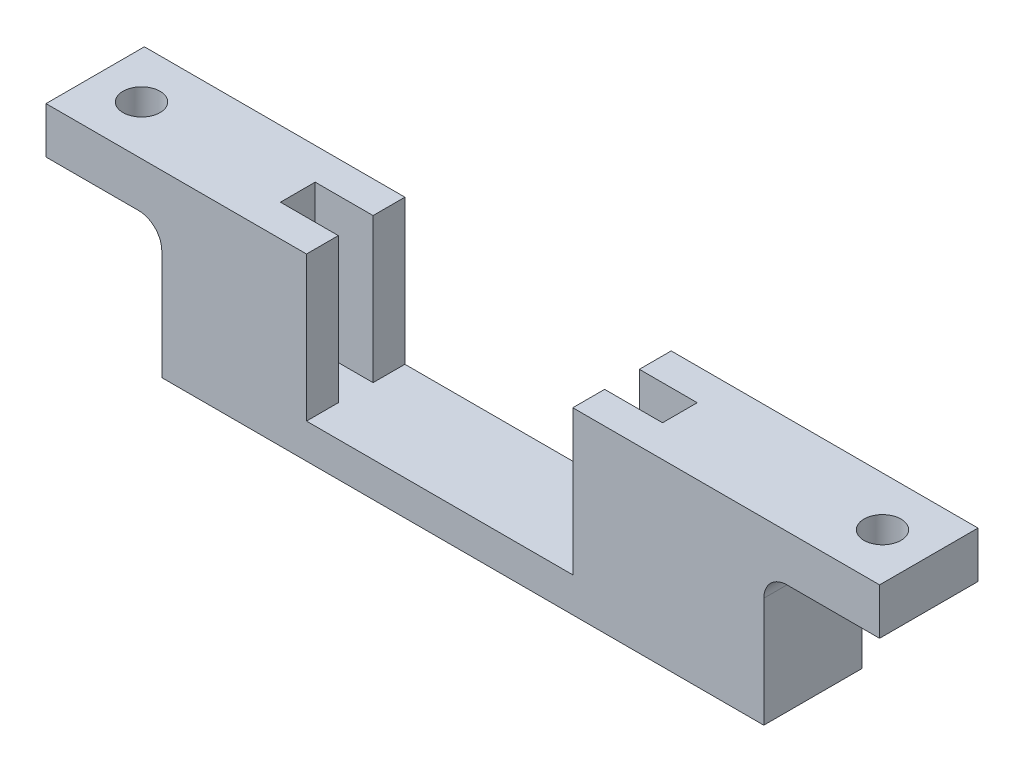
SolidWorks part; units mm, degrees
ref_plane "Front Plane" through (0, 0, 0) normal (0, 0, 1) x (1, 0, 0)
ref_plane "Top Plane" through (0, 0, 0) normal (0, 1, 0) x (1, 0, 0)
ref_plane "Right Plane" through (0, 0, 0) normal (1, 0, 0) x (0, 0, -1)
sketch "Sketch1" plane through (0, 0, 0) normal (0, 1, 0) x (1, 0, 0)
  line L1 (-36, 4.25) -> (36, 4.25)
  line L2 (-36, 4.25) -> (-36, -4.25)
  line L3 (-36, -4.25) -> (36, -4.25)
  line L4 (36, 4.25) -> (36, -4.25)
  line L5 (-36, 4.25) -> (36, -4.25) construction
  line L6 (-36, -4.25) -> (36, 4.25) construction
  point P0 (0, 0)
  dimension "D1" = 8.5
  dimension "D2" = 72
extrude "Boss-Extrude1" add sketch "Sketch1" along normal blind 15.5
sketch "Sketch2" plane through (0, 15.5, 0) normal (0, 1, 0) x (1, 0, 0)
  line L0 (-37.0107, -28.8692) -> (-13.0693, 36.9092) construction
  line L1 (16.1982, -28.8692) -> (40.1396, 36.9092) construction
  line L3 (-13.5, -4.25) -> (9.5, -4.25)
  line L8 (-13.5, -4.25) -> (-13.5, 4.25)
  line L9 (-13.5, 4.25) -> (9.5, 4.25)
  line L10 (9.5, -4.25) -> (9.5, 4.25)
  line L11 (-13.5, -4.25) -> (9.5, 4.25) construction
  line L12 (-13.5, 4.25) -> (9.5, -4.25) construction
  line L13 (-18.5, -1.5) -> (-13.5, -1.5)
  line L14 (-18.5, -1.5) -> (-18.5, 1.5)
  line L15 (-18.5, 1.5) -> (-13.5, 1.5)
  line L16 (-13.5, -1.5) -> (-13.5, 1.5)
  line L17 (-18.5, -1.5) -> (-13.5, 1.5) construction
  line L18 (-18.5, 1.5) -> (-13.5, -1.5) construction
  line L19 (9.5, -1.5) -> (14.5, -1.5)
  line L20 (9.5, -1.5) -> (9.5, 1.5)
  line L21 (9.5, 1.5) -> (14.5, 1.5)
  line L22 (14.5, -1.5) -> (14.5, 1.5)
  line L23 (9.5, -1.5) -> (14.5, 1.5) construction
  line L24 (9.5, 1.5) -> (14.5, -1.5) construction
  line L25 (36, 4.25) -> (-36, 4.25) construction
  line L26 (-36, 4.25) -> (-36, -4.25) construction
  point P2 (-2, 0)
  point P9 (12, 0)
  point P10 (-16, 0)
  point P22 (0, 0)
  point P23 (0, 0)
  point P24 (-25.04, 4.02)
  point P30 (-25.04, 4.02)
  line M15 (36, 4.25) -> (-36, 4.25)
  line M17 (-36, -4.25) -> (36, -4.25)
  dimension "D1" = 20
  dimension "D2" = 3
  dimension "D3" = 23
  dimension "D4" = 5
  dimension "D5" = 3
  dimension "D6" = 5
  dimension "D7" = 2
  dimension "D8" = 50
  dimension "D9" = 53.2089
  dimension "D10" = 6.54
  dimension "D11" = 2.52
  dimension "D12" = 70
extrude "Cut-Extrude1" cut sketch "Sketch2" against normal blind 12.5 contours L10 L8 M17 M15 | L15 L14 L13 L8 | L19 L22 L21 L10 region at (-2, 15.5, 0) region at (-16, 15.5, 0) region at (12, 15.5, 0)
sketch "Sketch3" plane through (0, 0, 0) normal (0, -1, 0) x (1, 0, 0)
  line L0 (36, -4.25) -> (-36, -4.25) construction
  line L1 (-36, 4.25) -> (-26, 4.25)
  line L2 (-36, 4.25) -> (-36, -4.25)
  line L3 (-36, -4.25) -> (-26, -4.25)
  line L4 (-26, 4.25) -> (-26, -4.25)
  line L6 (36, 4.25) -> (26, 4.25)
  line L7 (36, 4.25) -> (36, -4.25)
  line L8 (36, -4.25) -> (26, -4.25)
  line L9 (26, 4.25) -> (26, -4.25)
  dimension "D1" = 10
  dimension "D2" = 10
extrude "Cut-Extrude2" cut sketch "Sketch3" against normal blind 11.5
sketch "Sketch4" plane through (0, 15.5, 0) normal (0, 1, 0) x (1, 0, 0)
  line L0 (-36, 0) -> (36, 0) construction
  line L1 (-36, 4.25) -> (-36, -4.25) construction
  line L2 (36, -4.25) -> (36, 4.25) construction
  circle A0 centre (-32, 0) radius 1.6
  circle A1 centre (32, 0) radius 1.6
  point P10 (32.3146, 0)
  dimension "D1" = 3.2
  dimension "D2" = 3.2
  dimension "D3" = 4
  dimension "D4" = 4
extrude "Cut-Extrude3" cut sketch "Sketch4" against normal through all
fillet "Fillet1" radius 2 2 edges at (-26, 11.5, 0) (26, 11.5, 0)
